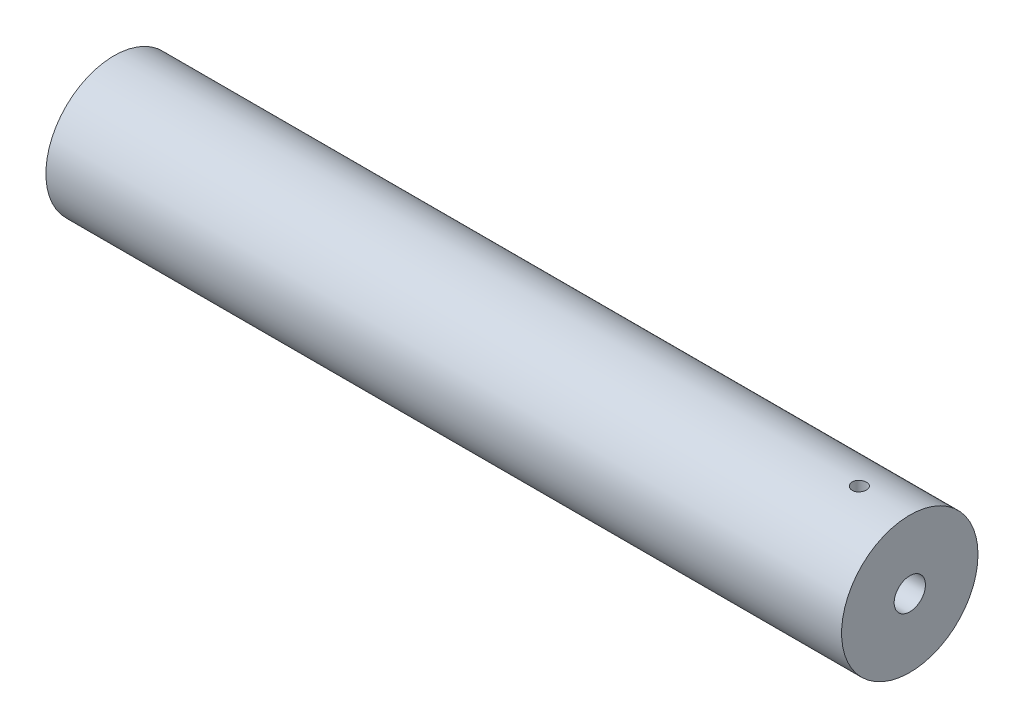
SolidWorks part; units mm, degrees
ref_plane "Front Plane" through (0, 0, 0) normal (0, 0, 1) x (1, 0, 0)
ref_plane "Top Plane" through (0, 0, 0) normal (0, 1, 0) x (1, 0, 0)
ref_plane "Right Plane" through (0, 0, 0) normal (1, 0, 0) x (0, 0, -1)
sketch "Sketch1" plane through (0, 0, 0) normal (1, 0, 0) x (0, 0, -1)
  circle A0 centre (0, 0) radius 12
  dimension "D1" = 24
extrude "Boss-Extrude1" add sketch "Sketch1" along normal blind 140
sketch "Sketch2" plane through (0, 0, 0) normal (0, 1, 0) x (1, 0, 0)
  circle A0 centre (131.1301, 0) radius 1.25
  dimension "D1" = 2.5
extrude "Cut-Extrude1" cut sketch "Sketch2" along normal blind 120 and the other way blind 120
sketch "Sketch3" plane through (140, 0, 0) normal (1, 0, 0) x (0, 0, -1)
  circle A0 centre (0, 0) radius 2.75
  dimension "D1" = 5.5
extrude "Cut-Extrude2" cut sketch "Sketch3" against normal blind 42
sketch "Sketch4" plane through (0, 0, 0) normal (-1, 0, 0) x (0, 0, 1)
  circle A0 centre (0, 0) radius 4
  dimension "D1" = 8
extrude "Cut-Extrude3" cut sketch "Sketch4" against normal blind 70
